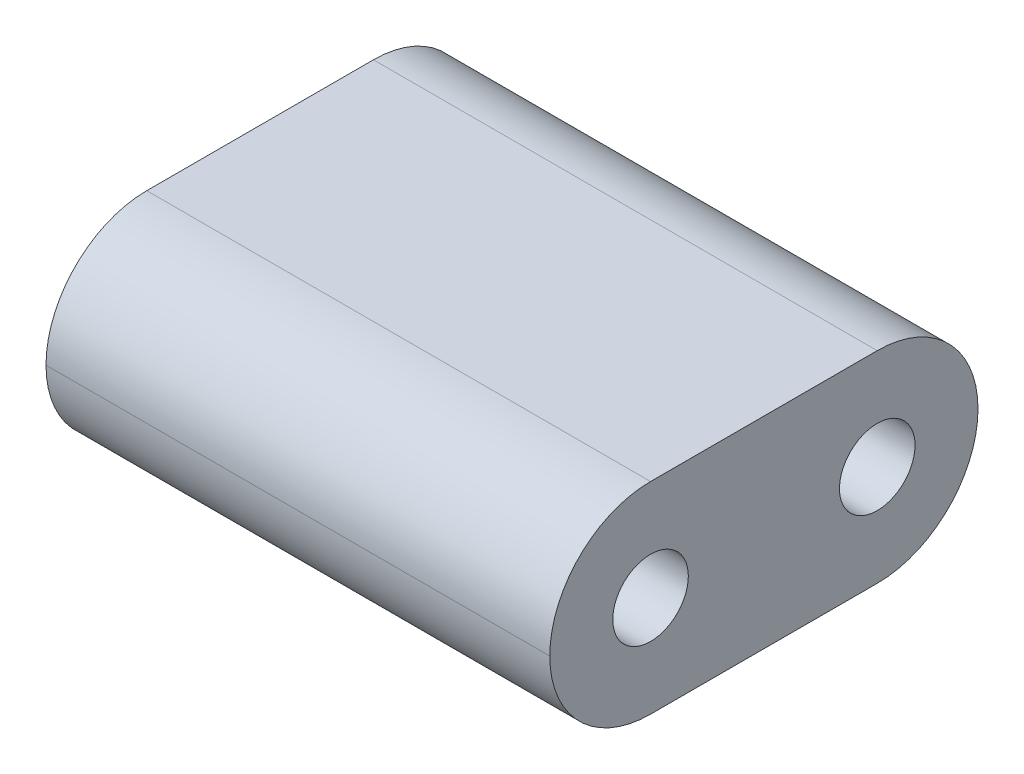
SolidWorks part; units mm, degrees
ref_plane "Front Plane" through (0, 0, 0) normal (0, 0, 1) x (1, 0, 0)
ref_plane "Top Plane" through (0, 0, 0) normal (0, 1, 0) x (1, 0, 0)
ref_plane "Right Plane" through (0, 0, 0) normal (1, 0, 0) x (0, 0, -1)
sketch "Sketch1" plane through (0, 0, 0) normal (0, 1, 0) x (1, 0, 0)
  line L1 (0, 0) -> (12.7, 0)
  line L2 (0, 0) -> (0, 10.795)
  line L3 (0, 10.795) -> (12.7, 10.795)
  line L4 (12.7, 0) -> (12.7, 10.795)
  dimension "D1" = 12.7
  dimension "D2" = 10.795
extrude "Boss-Extrude1" add sketch "Sketch1" along normal blind 5.08
sketch "Sketch2" plane through (12.7, 0, 0) normal (1, 0, 0) x (0, 0, -1)
  line L0 (0, 5.08) -> (0, 0) construction
  line L2 (0, 2.54) -> (11.5953, 2.54) construction
  line L3 (0, 5.08) -> (0, 0) construction
  line L4 (10.795, 5.08) -> (10.795, 0) construction
  circle A0 centre (2.54, 2.54) radius 0.9525
  circle A9 centre (8.255, 2.54) radius 0.9525
  dimension "D1" = 1.905
  dimension "D2" = 2.54
  dimension "D3" = 2.54
extrude "Cut-Extrude1" cut sketch "Sketch2" against normal up to next contours A0 | A9 | A0 | A9 region at (12.7, 2.54, -2.54) region at (12.7, 2.54, -8.255)
fillet "Fillet1" radius 2.54 4 edges at (6.35, 0, -10.795) (6.35, 5.08, -10.795) (6.35, 0, 0) (6.35, 5.08, 0)
